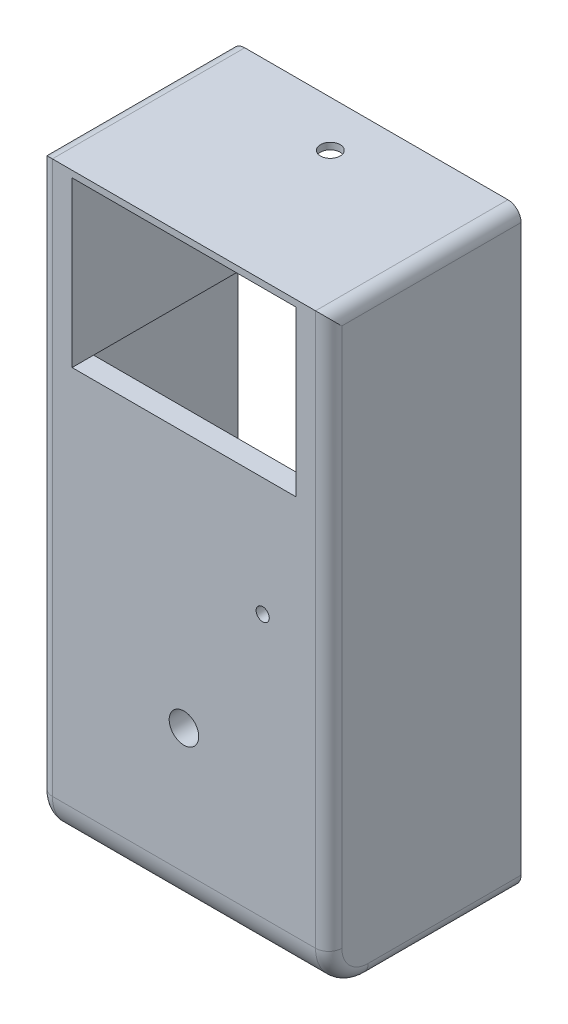
SolidWorks part; units mm, degrees
material "ABS"
ref_plane "前视基准面" through (0, 0, 0) normal (0, 0, 1) x (1, 0, 0)
ref_plane "上视基准面" through (0, 0, 0) normal (0, 1, 0) x (1, 0, 0)
ref_plane "右视基准面" through (0, 0, 0) normal (1, 0, 0) x (0, 0, -1)
sketch "草图1" plane through (0, 0, 0) normal (0, 0, 1) x (1, 0, 0)
  line L1 (0, 0) -> (340.4, 0)
  line L2 (0, 0) -> (0, -900)
  line L3 (0, -900) -> (340.4, -900)
  line L4 (340.4, 0) -> (340.4, -900)
  dimension "D1" = 340.4
  dimension "D2" = 900
extrude "凸台-拉伸1" add sketch "草图1" along normal blind 292.7
sketch "草图2" plane through (0, 0, 292.7) normal (0, 0, 1) x (1, 0, 0)
  line L0 (170.2, -900) -> (170.2, -650) construction
  line L1 (0, -900) -> (340.4, -900) construction
  circle A0 centre (170.2, -650) radius 22.5
  dimension "D2" = 45
  dimension "D1" = 250
extrude "切除-拉伸1" cut sketch "草图2" against normal through all
sketch "草图3" plane through (0, 0, 0) normal (0, 0, -1) x (-1, 0, 0)
  line L0 (-340.4, 0) -> (-390.4, 0)
  line L1 (-340.4, 0) -> (-340.4, -900)
  line L2 (-340.4, -900) -> (-390.4, -900)
  line L3 (-390.4, 0) -> (-390.4, -900)
  line L4 (0, 0) -> (50, 0)
  line L5 (50, 0) -> (50, -900)
  line L6 (50, -900) -> (0, -900)
  line L7 (0, -900) -> (0, 0)
  dimension "D1" = 50
  dimension "D2" = 50
extrude "凸台-拉伸2" add sketch "草图3" against normal blind 292.7
sketch "草图4" plane through (0, 0, 0) normal (0, 0, -1) x (-1, 0, 0)
  line L3 (-455, -5) -> (-455, -885)
  line L5 (35, -5) -> (35, -885)
  line L10 (-455, -885) -> (35, -885)
  line L11 (-455, -5) -> (35, -5)
fillet "圆角9" radius 20 6 edges at (390.4, 0, 146.35) (-50, 0, 146.35) (-50, -450, 292.7) (390.4, -450, 292.7) (-50, -900, 146.35) (390.4, -900, 146.35)
fillet "圆角10" radius 60 3 edges at (384.5421, -894.1421, 286.8421) (-44.1421, -894.1421, 286.8421) (170.2, -900, 292.7)
sketch "草图5" plane through (0, 0, 292.7) normal (0, 0, 1) x (1, 0, 0)
  line L0 (290, -440) -> (290, -840) construction
  line L1 (-30, -840) -> (370.4, -840) construction
  circle A1 centre (290, -440) radius 10
  dimension "D3" = 20
  dimension "D1" = 400
extrude "切除-拉伸3" cut sketch "草图5" against normal through all and the other way through all
sketch "草图6" plane through (0, 0, 0) normal (0, 1, 0) x (1, 0, 0)
  line L0 (170.2, 0) -> (170.2, -70) construction
  line L1 (370.4, 0) -> (-30, 0) construction
  circle A0 centre (170.2, -70) radius 15
  dimension "D2" = 30
  dimension "D1" = 70
extrude "切除-拉伸4" cut sketch "草图6" against normal up to next
sketch "草图7" plane through (0, 0, 0) normal (0, 0, -1) x (-1, 0, 0)
  line L1 (-380.4, -890) -> (40, -890)
  line L3 (-380.4, -260) -> (40, -260)
  line L5 (-380.4, -260) -> (-380.4, -890)
  line L8 (40, -890) -> (40, -260)
extrude "切除-拉伸6" cut sketch "草图7" against normal blind 260
sketch "草图8" plane through (0, 0, 292.7) normal (0, 0, 1) x (1, 0, 0)
  line L2 (170.2, -10) -> (0, -10)
  line L3 (0, -10) -> (0, -260)
  line L4 (170.2, -10) -> (340.4, -10)
  line L5 (0, -260) -> (340.4, -260)
  line L6 (340.4, -260) -> (340.4, -10)
  dimension "D2" = 170.2
  dimension "D3" = 250
  dimension "D4" = 170.2
extrude "切除-拉伸7" cut sketch "草图8" against normal through all
